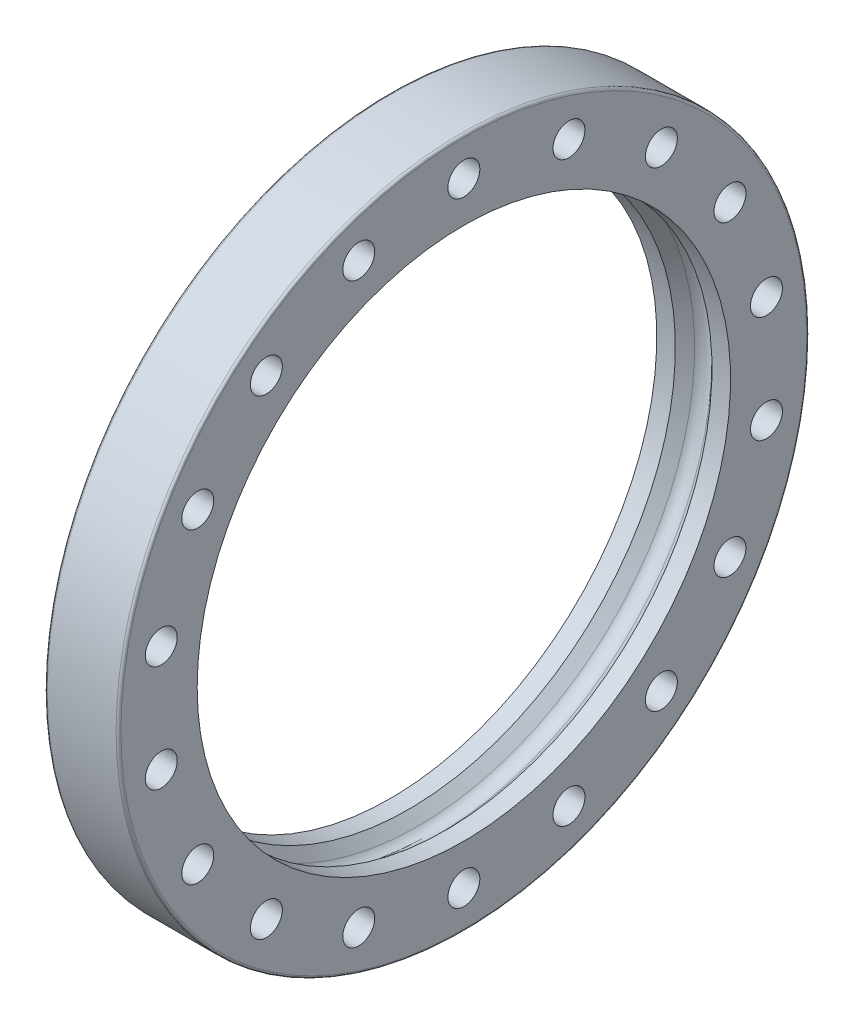
SolidWorks part; units mm, degrees
ref_plane "Front Plane" through (0, 0, 0) normal (0, 0, 1) x (1, 0, 0)
ref_plane "Top Plane" through (0, 0, 0) normal (0, 1, 0) x (1, 0, 0)
ref_plane "Right Plane" through (0, 0, 0) normal (1, 0, 0) x (0, 0, -1)
sketch "Sketch1" plane through (0, 0, 0) normal (0, 0, 1) x (1, 0, 0)
  line L0 (0, 0) -> (0, 124.5) construction
  line L1 (0, 115.9424) -> (9.1924, 106.75)
  line L2 (15, 140.5) -> (-15, 140.5)
  line L3 (15, 140.5) -> (15, 108.5)
  line L4 (15, 108.5) -> (-15, 108.5)
  line L5 (-15, 140.5) -> (-15, 108.5)
  line L6 (15, 140.5) -> (-15, 108.5) construction
  line L7 (15, 108.5) -> (-15, 140.5) construction
  line L8 (15, 105) -> (-15, 105) construction
  line L9 (15, 105) -> (15, 73) construction
  line L10 (15, 73) -> (-15, 73) construction
  line L11 (-15, 105) -> (-15, 73) construction
  line L12 (15, 105) -> (-15, 73) construction
  line L13 (15, 73) -> (-15, 105) construction
  line L14 (0, 115.9424) -> (-9.1924, 106.75)
  line L15 (9.1924, 106.75) -> (0, 97.5576)
  line L16 (-9.1924, 106.75) -> (0, 97.5576)
  line L17 (0, 115.9424) -> (0, 97.5576) construction
  line L18 (9.1924, 106.75) -> (-9.1924, 106.75) construction
  line L19 (0, 0) -> (135.8124, 0) construction
  point P7 (0, 89)
  point P13 (0, 106.75)
  dimension "D2" = 140.5
  dimension "D1" = 30
  dimension "D3" = 73
  dimension "D4" = 32
  dimension "D5" = 1.75
  dimension "D6" = 13
revolve "Revolve1" add sketch "Sketch1" angle 360 about L19 region at (0, 125.3278, 0)
fillet "Fillet1" radius 1 2 edges at (15, 0, 140.5) (-15, 0, 140.5)
fillet "Fillet2" radius 5 1 edges at (0, 0, 115.9424)
ref_axis "Axis1" through (14, 0, 0) along (-1, 0, 0)
sketch "Sketch2" plane through (15, 0, 0) normal (1, 0, 0) x (0, 0, -1)
  circle A0 centre (0, 0) radius 125 construction
  circle A1 centre (0, 125) radius 6.5
  dimension "D1" = 250
  dimension "D2" = 13
extrude "Cut-Extrude2" cut sketch "Sketch2" against normal through all
pattern_circular "CirPattern1" count 18 over 360 about axis through (14, 0, 0) along (-1, 0, 0) of "Cut-Extrude2"
